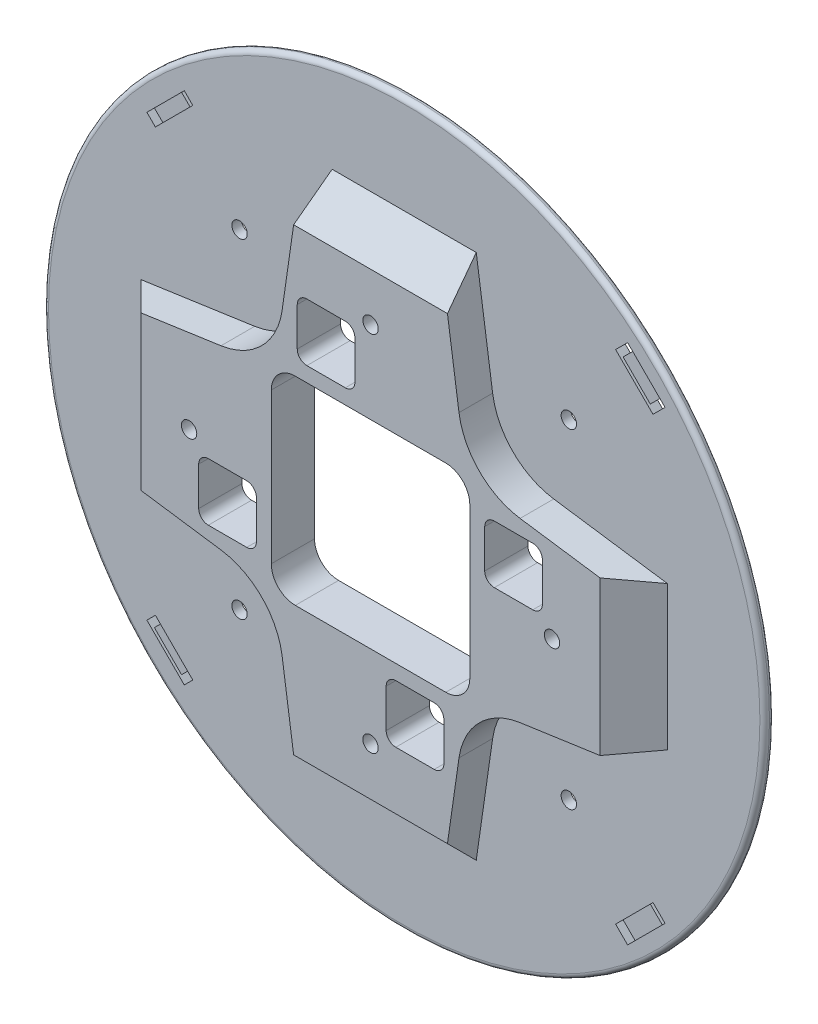
SolidWorks part; units mm, degrees
ref_plane "Front" through (0, 0, 0) normal (0, 0, 1) x (1, 0, 0)
ref_plane "Top" through (0, 0, 0) normal (0, 1, 0) x (1, 0, 0)
ref_plane "Right" through (0, 0, 0) normal (1, 0, 0) x (0, 0, -1)
sketch "ｽｹｯﾁ1" plane through (0, 0, 0) normal (0, 0, 1) x (1, 0, 0)
  line L1 (47.75, -47.75) -> (-47.75, -47.75)
  line L2 (47.75, -47.75) -> (47.75, 47.75)
  line L3 (47.75, 47.75) -> (-47.75, 47.75)
  line L4 (-47.75, -47.75) -> (-47.75, 47.75)
  line L5 (47.75, -47.75) -> (-47.75, 47.75) construction
  line L6 (47.75, 47.75) -> (-47.75, -47.75) construction
  point P0 (0, 0)
  dimension "D1" = 95.5
extrude "ﾎﾞｽ - 押し出し1" add sketch "ｽｹｯﾁ1" along normal blind 7
sketch "ｽｹｯﾁ2" plane through (0, 0, 7) normal (0, 0, 1) x (1, 0, 0)
  line L0 (-16, 47.75) -> (-20, 20)
  line L2 (-20, 20) -> (-47.75, 16)
  line L4 (-47.75, 16) -> (-47.75, 47.75)
  line L5 (-47.75, 47.75) -> (-16, 47.75)
  line L6 (-16, -47.75) -> (-20, -20)
  line L8 (-20, -20) -> (-47.75, -16)
  line L9 (-47.75, -16) -> (-47.75, -47.75)
  line L10 (-47.75, -47.75) -> (-16, -47.75)
  line L11 (0, 0) -> (-47.75, 47.75) construction
  line L12 (0, 0) -> (-47.75, -47.75) construction
  line L13 (-47.75, 47.75) -> (-47.75, -47.75) construction
  line L14 (-47.75, -47.75) -> (47.75, -47.75) construction
  dimension "D1" = 16
  dimension "D2" = 16
  dimension "D3" = 16
  dimension "D4" = 4
  dimension "D5" = 4
extrude "ｶｯﾄ - 押し出し1" cut sketch "ｽｹｯﾁ2" against normal through all
mirror "ﾐﾗｰ1" about plane through (0, 0, 0) normal (1, 0, 0) of "ｶｯﾄ - 押し出し1"
fillet "ﾌｨﾚｯﾄ2" radius 15 4 edges at (-20, 20, 3.5) (20, 20, 3.5) (20, -20, 3.5) (-20, -20, 3.5)
sketch "ｽｹｯﾁ3" plane through (0, 0, 0) normal (0, 0, -1) x (-1, 0, 0)
  circle A0 centre (0, 0) radius 75
  dimension "D1" = 150
extrude "ﾎﾞｽ - 押し出し2" add sketch "ｽｹｯﾁ3" along normal blind 2
chamfer "面取り1" distance 7 angle 45 4 edges at (0, 47.75, 0) (47.75, 0, 0) (0, -47.75, 0) (-47.75, 0, 0)
fillet "ﾌｨﾚｯﾄ1" radius 1 2 edges at (-75, 0, 0) (-75, 0, -2)
sketch "ｽｹｯﾁ5" plane through (0, 0, 0) normal (0, 0, 1) x (1, 0, 0)
  circle A0 centre (-34.25, 34.25) radius 1.6
  circle A1 centre (34.25, 34.25) radius 1.6
  circle A2 centre (34.25, -34.25) radius 1.6
  circle A3 centre (-34.25, -34.25) radius 1.6
  dimension "D1" = 3.2
extrude "ｶｯﾄ - 押し出し2" cut sketch "ｽｹｯﾁ5" against normal through all
sketch "ｽｹｯﾁ6" plane through (0, 0, 7) normal (0, 0, 1) x (1, 0, 0)
  line L1 (21, -21) -> (-21, -21)
  line L2 (21, -21) -> (21, 21)
  line L3 (21, 21) -> (-21, 21)
  line L4 (-21, -21) -> (-21, 21)
  line L5 (21, -21) -> (-21, 21) construction
  line L6 (21, 21) -> (-21, -21) construction
  point P0 (0, 0)
  dimension "D1" = 42
extrude "ｶｯﾄ - 押し出し3" cut sketch "ｽｹｯﾁ6" against normal through all
sketch "ｽｹｯﾁ7" plane through (0, 0, 7) normal (0, 0, 1) x (1, 0, 0)
  line L4 (-47.75, 16) -> (-47.75, -16) construction
  line L5 (-16, -47.75) -> (16, -47.75) construction
  line L6 (47.75, -16) -> (47.75, 16) construction
  line L7 (16, 47.75) -> (-16, 47.75) construction
  circle A0 centre (0, 37.75) radius 1.6
  circle A1 centre (-37.75, 0) radius 1.6
  circle A2 centre (37.75, 0) radius 1.6
  circle A3 centre (0, -37.75) radius 1.6
  dimension "D1" = 3.2
  dimension "D2" = 10
  dimension "D3" = 10
  dimension "D4" = 10
  dimension "D5" = 10
extrude "ｶｯﾄ - 押し出し4" cut sketch "ｽｹｯﾁ7" against normal through all
chamfer "面取り2" [suppressed] distance 1.5 angle 45
sketch "ｽｹｯﾁ8" plane through (0, 0, -2) normal (0, 0, -1) x (-1, 0, 0)
  line L0 (52.3259, -52.3259) -> (-52.3259, 52.3259) construction
  line L1 (-52.3259, -52.3259) -> (52.3259, 52.3259) construction
  line L2 (-47.5416, 53.1985) -> (-45.0416, 50.6985)
  line L3 (-45.0416, 50.6985) -> (-43.981, 51.7591)
  line L4 (-43.981, 51.7591) -> (-46.481, 54.2591)
  line L5 (-46.481, 54.2591) -> (-47.5416, 53.1985)
  line L6 (-53.1985, 47.5416) -> (-54.2591, 46.481)
  line L7 (-54.2591, 46.481) -> (-51.7591, 43.981)
  line L8 (-51.7591, 43.981) -> (-50.6985, 45.0416)
  line L9 (-50.6985, 45.0416) -> (-53.1985, 47.5416)
  line L10 (45.7487, 53.5269) -> (43.981, 51.7591)
  line L11 (43.981, 51.7591) -> (45.0416, 50.6985)
  line L12 (45.0416, 50.6985) -> (46.8094, 52.4663)
  line L13 (46.8094, 52.4663) -> (45.7487, 53.5269)
  line L14 (52.4663, 46.8094) -> (50.6985, 45.0416)
  line L15 (50.6985, 45.0416) -> (51.7591, 43.981)
  line L16 (51.7591, 43.981) -> (53.5269, 45.7487)
  line L17 (53.5269, 45.7487) -> (52.4663, 46.8094)
  circle A0 centre (0, 0) radius 74 construction
  point P6 (0, 0)
  point P10 (0, 0)
  dimension "D1" = 2.5
  dimension "D2" = 1.5
  dimension "D3" = 4
  dimension "D4" = 8
  dimension "D5" = 38
  dimension "D6" = 1.5
  dimension "D7" = 2.5
  dimension "D8" = 4
  dimension "D9" = 8
  dimension "D10" = 38
extrude "ｶｯﾄ - 押し出し5" cut sketch "ｽｹｯﾁ8" against normal through all
sketch "ｽｹｯﾁ9" plane through (0, 0, 0) normal (0, 0, 1) x (1, 0, 0)
  line L0 (-53.5269, 45.7487) -> (-45.7487, 53.5269)
  line L1 (-45.7487, 53.5269) -> (-43.981, 51.7591)
  line L2 (-43.981, 51.7591) -> (-51.7591, 43.981)
  line L3 (-51.7591, 43.981) -> (-53.5269, 45.7487)
  line L4 (46.481, 54.2591) -> (43.981, 51.7591)
  line L5 (43.981, 51.7591) -> (51.7591, 43.981)
  line L6 (51.7591, 43.981) -> (54.2591, 46.481)
  line L7 (54.2591, 46.481) -> (46.481, 54.2591)
extrude "ｶｯﾄ - 押し出し6" cut sketch "ｽｹｯﾁ9" against normal blind 0.5
mirror "ﾐﾗｰ2" about plane through (0, 0, 0) normal (0, 1, 0) of "ｶｯﾄ - 押し出し6", "ｶｯﾄ - 押し出し5"
sketch "ｽｹｯﾁ10" plane through (0, 0, 7) normal (0, 0, 1) x (1, 0, 0)
  line L0 (23.75, -3.75) -> (23.75, 20.75) construction
  line L1 (-35.75, -3.25) -> (-23.75, -3.25)
  line L2 (-35.75, -3.25) -> (-35.75, -15.25)
  line L3 (-35.75, -15.25) -> (-23.75, -15.25)
  line L4 (-23.75, -3.25) -> (-23.75, -15.25)
  line L5 (-15.25, 35.75) -> (-3.25, 35.75)
  line L6 (-15.25, 35.75) -> (-15.25, 23.75)
  line L7 (-15.25, 23.75) -> (-3.25, 23.75)
  line L8 (-3.25, 35.75) -> (-3.25, 23.75)
  line L9 (23.75, 3.25) -> (35.75, 3.25)
  line L10 (23.75, 3.25) -> (23.75, 15.25)
  line L11 (23.75, 15.25) -> (35.75, 15.25)
  line L12 (35.75, 3.25) -> (35.75, 15.25)
  line L13 (15.25, -23.75) -> (3.25, -23.75)
  line L14 (15.25, -23.75) -> (15.25, -35.75)
  line L15 (15.25, -35.75) -> (3.25, -35.75)
  line L16 (3.25, -23.75) -> (3.25, -35.75)
  line L18 (3.75, 23.75) -> (-20.75, 23.75) construction
  line L21 (-23.75, 3.75) -> (-23.75, -20.75) construction
  line L23 (-3.75, -23.75) -> (20.75, -23.75) construction
  line L27 (-3.25, 33.75) -> (-3.25, 25.75) construction
  line L29 (33.75, 3.25) -> (25.75, 3.25) construction
  line L31 (-33.75, -3.25) -> (-25.75, -3.25) construction
  line L33 (-15.25, 25.75) -> (-15.25, 33.75) construction
  line L34 (35.75, 5.25) -> (35.75, 13.25) construction
  line L36 (3.25, -33.75) -> (3.25, -25.75) construction
  line L37 (15.25, -25.75) -> (15.25, -33.75) construction
  line L38 (-33.75, -15.25) -> (-25.75, -15.25) construction
extrude "ｶｯﾄ - 押し出し7" cut sketch "ｽｹｯﾁ10" against normal through all
sketch "ｽｹｯﾁ11" plane through (0, 0, -2) normal (0, 0, -1) x (-1, 0, 0)
  line L1 (-21, 21) -> (21, 21)
  line L2 (-21, 21) -> (-21, -21)
  line L3 (-21, -21) -> (21, -21)
  line L4 (21, 21) -> (21, -21)
extrude "ﾎﾞｽ - 押し出し4" add sketch "ｽｹｯﾁ11" against normal through all
fillet "ﾌｨﾚｯﾄ3" radius 2 16 edges at (23.75, 3.25, 2.5) (23.75, 15.25, 2.5) (35.75, 15.25, 2.5) (35.75, 3.25, 2.5) (15.25, -23.75, 2.5) (15.25, -35.75, 2.5) (3.25, -35.75, 2.5) (3.25, -23.75, 2.5) (-35.75, -3.25, 2.5) (-23.75, -3.25, 2.5) (-23.75, -15.25, 2.5) (-35.75, -15.25, 2.5) (-15.25, 23.75, 2.5) (-3.25, 23.75, 2.5) (-15.25, 35.75, 2.5) (-3.25, 35.75, 2.5)
sketch "ｽｹｯﾁ12" plane through (0, 0, 7) normal (0, 0, 1) x (1, 0, 0)
  line L1 (20.65, -20.65) -> (-20.65, -20.65)
  line L2 (20.65, -20.65) -> (20.65, 20.65)
  line L3 (20.65, 20.65) -> (-20.65, 20.65)
  line L4 (-20.65, -20.65) -> (-20.65, 20.65)
  line L5 (20.65, -20.65) -> (-20.65, 20.65) construction
  line L6 (20.65, 20.65) -> (-20.65, -20.65) construction
  point P0 (0, 0)
  dimension "D1" = 41.3
extrude "ｶｯﾄ - 押し出し8" cut sketch "ｽｹｯﾁ12" against normal through all
fillet "ﾌｨﾚｯﾄ4" radius 5 4 edges at (-20.65, -20.65, 2.5) (20.65, -20.65, 2.5) (20.65, 20.65, 2.5) (-20.65, 20.65, 2.5)
sketch "ｽｹｯﾁ13" plane through (0, 0, -2) normal (0, 0, -1) x (-1, 0, 0)
  circle A0 centre (-37.75, 0) radius 3.25
  circle A1 centre (0, -37.75) radius 3.25
  circle A2 centre (37.75, 0) radius 3.25
  circle A3 centre (0, 37.75) radius 3.25
  dimension "D1" = 6.5
extrude "ｶｯﾄ - 押し出し9" cut sketch "ｽｹｯﾁ13" against normal blind 2
